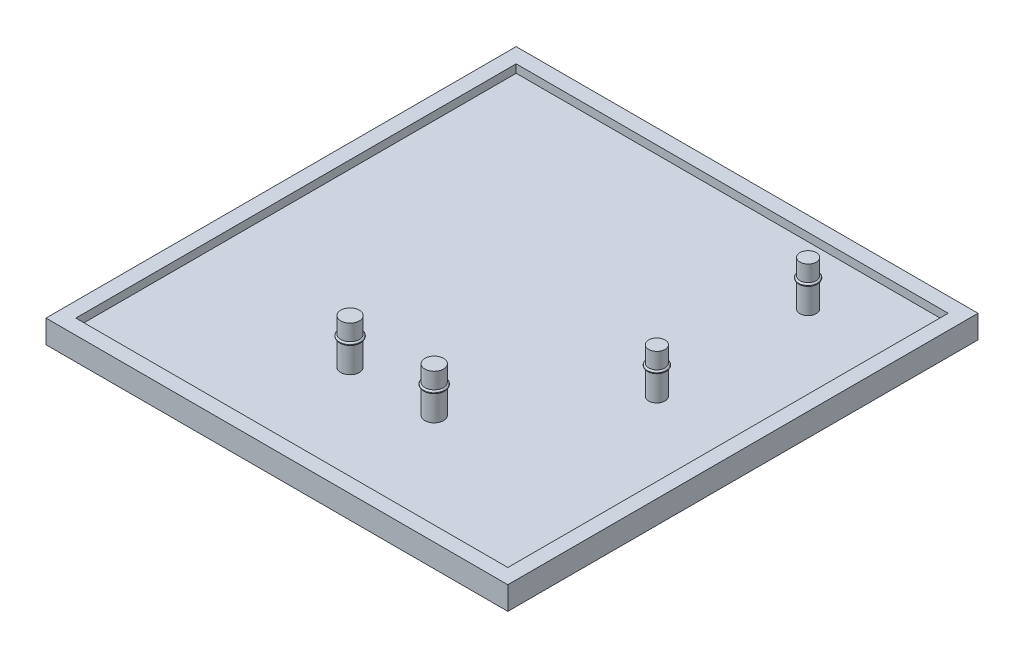
SolidWorks part; units mm, degrees
ref_plane "Front Plane" through (0, 0, 0) normal (0, 0, 1) x (1, 0, 0)
ref_plane "Top Plane" through (0, 0, 0) normal (0, 1, 0) x (1, 0, 0)
ref_plane "Right Plane" through (0, 0, 0) normal (1, 0, 0) x (0, 0, -1)
sketch "Sketch3" plane through (0, 0, 0) normal (0, 1, 0) x (1, 0, 0)
  line L1 (0, 0) -> (78.7146, 0)
  line L2 (0, 0) -> (0, 80.137)
  line L3 (0, 80.137) -> (78.7146, 80.137)
  line L4 (78.7146, 0) -> (78.7146, 80.137)
  dimension "D1" = 78.7146
  dimension "D2" = 80.137
extrude "Boss-Extrude1" add sketch "Sketch3" along normal blind 3.937 contours L3 L4 L1 L2
shell "Shell1" thickness 2.54 removed face at (39.3573, 3.937, -40.0685)
sketch "Sketch4" plane through (0, 2.54, 0) normal (0, 1, 0) x (1, 0, 0)
  line L2 (76.1746, 2.54) -> (76.1746, 77.597) construction
  line L3 (2.54, 77.597) -> (76.1746, 77.597) construction
  line L4 (76.1746, 2.54) -> (76.1746, 77.597) construction
  line L5 (2.54, 2.54) -> (76.1746, 2.54) construction
  line L7 (2.54, 2.54) -> (2.54, 77.597) construction
  circle A0 centre (62.2046, 67.691) radius 1.397
  circle A1 centre (62.2046, 41.91) radius 1.397
  circle A2 centre (46.0375, 20.1295) radius 1.5875
  circle A3 centre (31.7627, 20.066) radius 1.5875
  dimension "D1" = 3.175
  dimension "D2" = 3.175
  dimension "D3" = 2.794
  dimension "D4" = 2.794
  dimension "D5" = 9.906
  dimension "D6" = 13.97
  dimension "D7" = 13.97
  dimension "D8" = 39.37
  dimension "D9" = 17.5895
  dimension "D10" = 17.526
  dimension "D11" = 30.1371
  dimension "D12" = 29.2227
extrude "Boss-Extrude2" add sketch "Sketch4" along normal blind 7.62
ref_plane "Plane1" through (0, 6.9088, 0) normal (0, -1, 0) x (-1, 0, 0)
sketch "Sketch7" plane through (0, 6.9088, 0) normal (0, -1, 0) x (-1, 0, 0)
  circle A0 centre (-31.7627, 20.066) radius 1.8415
  circle A1 centre (-46.0375, 20.1295) radius 1.8415
  circle A2 centre (-62.2046, 41.91) radius 1.651
  circle A3 centre (-62.2046, 67.691) radius 1.651
  dimension "D1" = 3.683
  dimension "D2" = 3.683
  dimension "D3" = 3.302
  dimension "D4" = 3.302
extrude "Boss-Extrude3" add sketch "Sketch7" against normal blind 0.508 separate body
fillet "Fillet1" radius 0.254 2 edges at (46.0375, 6.9088, -21.971) (46.0375, 7.4168, -21.971)
fillet "Fillet2" radius 0.254 2 edges at (31.7627, 6.9088, -21.9075) (31.7627, 7.4168, -21.9075)
fillet "Fillet4" radius 0.254 2 edges at (62.2046, 6.9088, -43.561) (62.2046, 7.4168, -43.561)
fillet "Fillet5" radius 0.254 2 edges at (62.2046, 6.9088, -69.342) (62.2046, 7.4168, -69.342)
equation "\"hole1_hor_distance\"= .493"
equation "\"hole1_diameter\" = 0.11"
equation "\"hole2_diameter\" = 0.125"
equation "\"hole2_vert_distance\" = 0.63"
